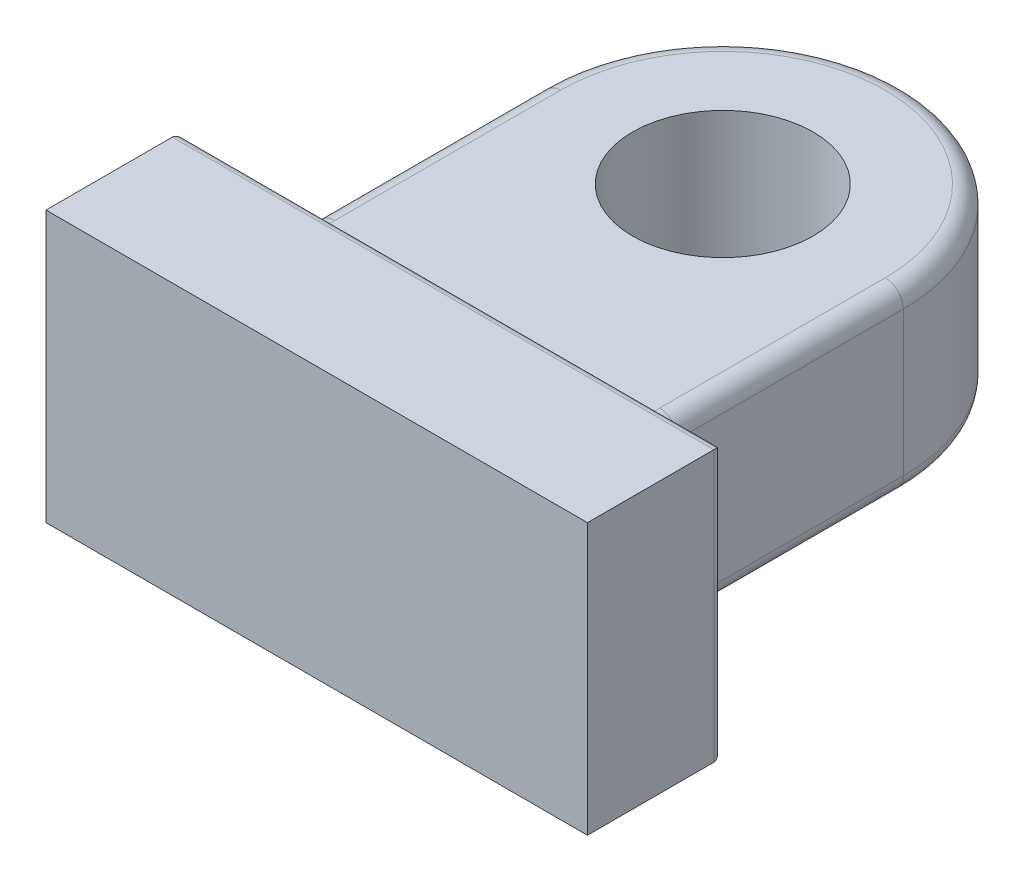
SolidWorks part; units mm, degrees
ref_plane "Front Plane" through (0, 0, 0) normal (0, 0, 1) x (1, 0, 0)
ref_plane "Top Plane" through (0, 0, 0) normal (0, 1, 0) x (1, 0, 0)
ref_plane "Right Plane" through (0, 0, 0) normal (1, 0, 0) x (0, 0, -1)
sketch "Sketch1" plane through (0, 0, 0) normal (0, 0, 1) x (1, 0, 0)
  line L1 (0, 0) -> (60, 0)
  line L2 (0, 0) -> (0, -30)
  line L3 (0, -30) -> (60, -30)
  line L4 (60, 0) -> (60, -30)
  dimension "D1" = 60
  dimension "D2" = 30
extrude "Boss-Extrude1" add sketch "Sketch1" along normal blind 15
ref_plane "Plane1" through (0, -15, 0) normal (0, 1, 0) x (1, 0, 0)
sketch "Sketch2" plane through (0, -15, 0) normal (0, 1, 0) x (1, 0, 0)
  line L0 (10, 30) -> (10, 0)
  line L1 (60, 0) -> (0, 0) construction
  line L2 (10, 0) -> (50, 0)
  line L3 (50, 0) -> (50, 30)
  line L4 (60, -15) -> (60, 0) construction
  circle A0 centre (30, 30) radius 10
  arc A1 (50, 30) -> (10, 30) centre (30, 30) ccw
  dimension "D1" = 20
  dimension "D2" = 20
  dimension "D3" = 30
  dimension "D4" = 10
extrude "Boss-Extrude2" add sketch "Sketch2" along normal mid plane 20
fillet "Fillet1" radius 5 2 edges at (10, -15, 0) (50, -15, 0)
fillet "Fillet2" radius 2 10 edges at (51.4645, -25, -1.4645) (50, -25, -17.5) (8.5355, -25, -1.4645) (10, -25, -17.5) (51.4645, -5, -1.4645) (50, -5, -17.5) (8.5355, -5, -1.4645) (10, -5, -17.5) (30, -25, -50) (30, -5, -50)
fillet "Fillet3" radius 1 10 edges at (30, -30, 0) (60, -15, 0) (30, 0, 0) (0, -15, 0) (51.6773, -5.266, 0) (51.6773, -24.734, 0) (30, -25, 0) (8.3227, -24.734, 0) (8.3227, -5.266, 0) (30, -5, 0)
sketch "Sketch3" plane through (0, 0, 15) normal (0, 0, 1) x (1, 0, 0)
  line L0 (30, 0) -> (30, -30) construction
  line L1 (60, 0) -> (0, 0) construction
  line L2 (0, -30) -> (60, -30) construction
